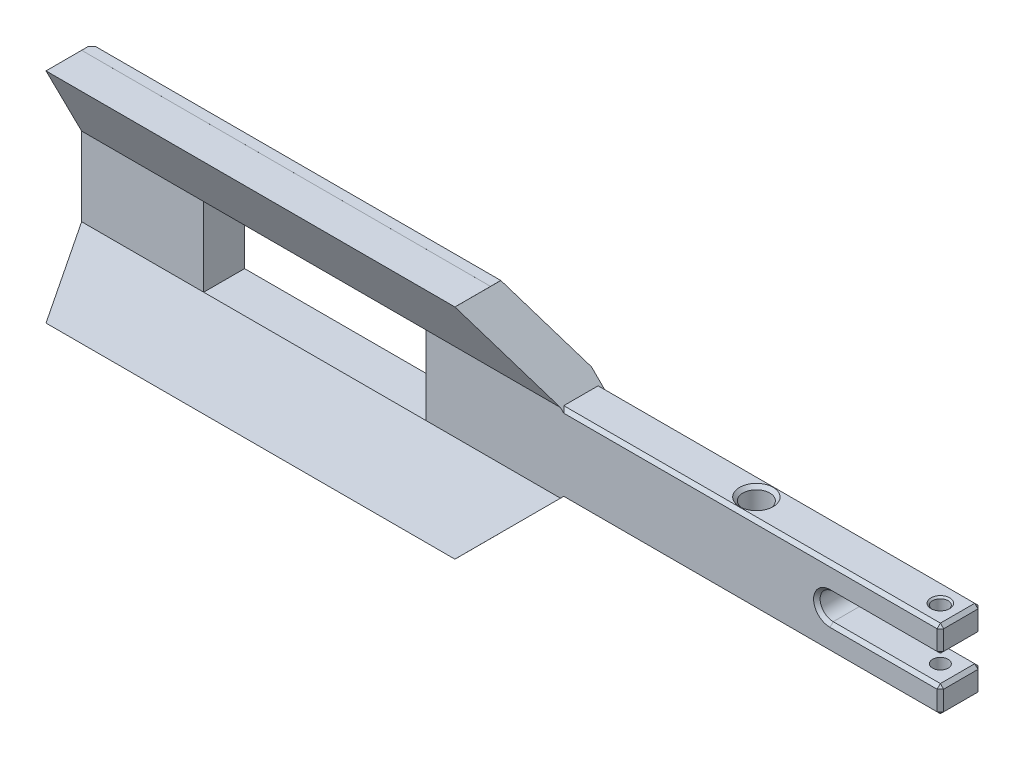
SolidWorks part; units mm, degrees
ref_plane "Front" through (0, 0, 0) normal (0, 0, 1) x (1, 0, 0)
ref_plane "Top" through (0, 0, 0) normal (0, 1, 0) x (1, 0, 0)
ref_plane "Right" through (0, 0, 0) normal (1, 0, 0) x (0, 0, -1)
sketch "Sketch1" plane through (0, 0, 0) normal (0, 0, 1) x (1, 0, 0)
  line L1 (52.5, -4.8) -> (-52.5, -4.8)
  line L2 (52.5, -4.8) -> (52.5, 4.8)
  line L3 (52.5, 4.8) -> (-52.5, 4.8)
  line L4 (-52.5, -4.8) -> (-52.5, 4.8)
  line L5 (52.5, -4.8) -> (-52.5, 4.8) construction
  line L6 (52.5, 4.8) -> (-52.5, -4.8) construction
  point P0 (0, 0)
  dimension "D1" = 9.6
  dimension "D2" = 105
extrude "Boss-Extrude1" add sketch "Sketch1" along normal blind 5
sketch "Sketch2" plane through (0, 4.8, 0) normal (0, 1, 0) x (1, 0, 0)
  line L0 (52.5, -5) -> (52.5, 0) construction
  line L2 (52.5, 0) -> (-52.5, 0) construction
  circle A0 centre (27.5, -2.5) radius 1.65
  dimension "D3" = 3.3
  dimension "D1" = 2.5
  dimension "D2" = 25
sketch "Sketch4" plane through (0, 0, 5) normal (0, 0, 1) x (1, 0, 0)
  line L0 (39, 0) -> (45, 0) construction
  line L1 (39, 1.6) -> (45, 1.6)
  line L2 (39, -1.6) -> (45, -1.6)
  arc A0 (39, 1.6) -> (39, -1.6) centre (39, 0) ccw
  arc A1 (45, -1.6) -> (45, 1.6) centre (45, 0) ccw
  point P2 (42, 0)
  dimension "D1" = 1.6
  dimension "D2" = 42
  dimension "D3" = 6
extrude "Cut-Extrude1" cut sketch "Sketch4" against normal blind 5
sketch "Sketch14" plane through (0, 0, 5) normal (0, 0, 1) x (1, 0, 0)
  line L0 (39, -1.6) -> (45, -1.6) construction
  line L1 (44.5, -1.6) -> (52.5, -1.6)
  line L2 (44.5, -1.6) -> (44.5, 1.6)
  line L3 (44.5, 1.6) -> (52.5, 1.6)
  line L4 (52.5, -1.6) -> (52.5, 1.6)
  line L5 (52.5, -4.8) -> (52.5, 4.8) construction
  line L6 (45, 1.6) -> (39, 1.6) construction
  dimension "D1" = 8
extrude "Cut-Extrude7" cut sketch "Sketch14" against normal blind 10
sketch "Sketch8" plane through (0, 0, 0) normal (0, 0, -1) x (-1, 0, 0)
  line L0 (52.5, 4.8) -> (52.5, -4.8) construction
  line L1 (52.5, 13.355) -> (2.5, 13.355)
  line L2 (52.5, 13.355) -> (52.5, -13.355)
  line L3 (52.5, -13.355) -> (2.5, -13.355)
  line L4 (2.5, 13.355) -> (2.5, -13.355)
  line L5 (2.5, 0) -> (52.5, 0) construction
  line L7 (-52.5, 0) -> (53.7381, 0) construction
  dimension "D1" = 26.71
  dimension "D3" = 50
extrude "Boss-Extrude3" add sketch "Sketch8" against normal up to surface (5 mm away) up to face at (22.675, 0, 5)
sketch "Sketch9" plane through (-52.5, 0, 0) normal (-1, 0, 0) x (0, 0, 1)
  line L0 (5, 13.355) -> (5, -13.355) construction
  line L1 (5, 13.3543) -> (9.357, 13.3543)
  line L2 (9.357, 13.3543) -> (5, 4.8)
  line L3 (5, 4.8) -> (5, 13.3543)
  line L4 (-3.9634, 0) -> (12.9509, 0) construction
  line L5 (9.357, -13.3543) -> (5, -4.8)
  line L6 (5, -13.3543) -> (9.357, -13.3543)
  line L7 (5, -4.8) -> (5, -13.3543)
  circle A0 centre (25, 0) radius 20 construction
  dimension "D1" = 40
  dimension "D2" = 9.6
  dimension "D3" = 9.6
extrude "Boss-Extrude4" add sketch "Sketch9" against normal up to surface (50 mm away) up to face at (-2.5, 9.0775, 2.5)
sketch "Sketch13" plane through (-52.5, 0, 0) normal (-1, 0, 0) x (0, 0, 1)
  line L0 (0, 6) -> (3.7462, 13.355)
  line L1 (0, 13.355) -> (0, -13.355) construction
  line L2 (5, 13.355) -> (0, 13.355) construction
  line L3 (3.7462, 13.355) -> (-2, 13.355)
  line L4 (-2, 13.355) -> (-2, -13.355)
  line L5 (-2, -13.355) -> (3.7462, -13.355)
  line L6 (5, -13.355) -> (0, -13.355) construction
  line L7 (3.7462, -13.355) -> (0, -6)
  line L8 (0, -6) -> (0, 6)
  line L10 (5, 4.8) -> (9.357, 13.3543) construction
  line L11 (9.357, -13.3543) -> (5, -4.8) construction
  dimension "D1" = 5
  dimension "D2" = 5
  dimension "D3" = 2
extrude "Cut-Extrude6" cut sketch "Sketch13" against normal through all
chamfer "Chamfer4" distance 8.55 2 edges at (-2.5, 4.8, 2.5) (-2.5, -4.8, 2.5)
sketch "Sketch10" plane through (-52.5, 0, 0) normal (-1, 0, 0) x (0, 0, 1)
  line L0 (5, 4.8) -> (5, -4.8) construction
  line L1 (5, 4.8) -> (9.357, 13.3543) construction
  line L2 (9.357, -13.3543) -> (5, -4.8) construction
  circle A0 centre (25, 0) radius 20
ref_plane "Plane1" through (-48.5, 0, 0) normal (-1, 0, 0) x (0, 0, 1)
extrude "Cut-Extrude5" cut sketch "Sketch2" against normal blind 10
chamfer "Chamfer5" distance 0.4 angle 45 20 edges at (25.85, -4.8, 2.5) (25.85, 4.8, 2.5) (52.5, 4.8, 2.5) (29.275, 4.8, 5) (52.5, -3.2, 5) (52.5, 3.2, 5) (29.275, -4.8, 5) (52.5, -4.8, 2.5) (29.275, 4.8, 0) (29.275, -4.8, 0) (52.5, 3.2, 0) (52.5, -3.2, 0) (45.75, -1.6, 0) (37.4, 0, 0) (45.75, 1.6, 0) (45.75, 1.6, 5) (37.4, 0, 5) (45.75, -1.6, 5) (52.5, 1.6, 2.5) (52.5, -1.6, 2.5)
chamfer "Chamfer6" distance 0.4 angle 45 3 edges at (-52.5, 9.6775, 1.8731) (-52.5, -9.6775, 1.8731) (-52.5, 0, 0)
sketch "Sketch15" plane through (0, -4.8, 0) normal (0, -1, 0) x (1, 0, 0)
  line L0 (52.5, 4.6) -> (52.5, 0.4) construction
  line L1 (52.1, 0) -> (6.45, 0) construction
  circle A0 centre (50, 2.5) radius 0.95
  dimension "D1" = 1.9
  dimension "D2" = 2.5
  dimension "D3" = 2.5
extrude "Cut-Extrude8" cut sketch "Sketch15" against normal blind 10
chamfer "Chamfer11" distance 0.2 angle 45 2 edges at (50.95, 4.8, 2.5) (50.95, -4.8, 2.5)
sketch "Sketch16" plane through (0, 0, 5) normal (0, 0, 1) x (1, 0, 0)
  line L1 (-10.4, 4.8) -> (-37.5733, 4.8)
  line L3 (-37.5733, -4.8) -> (-10.4, -4.8)
  line L7 (6.05, 4.8) -> (-52.5, 4.8) construction
  line L8 (6.05, -4.8) -> (-52.5, -4.8) construction
  line L11 (-37.5733, 4.8) -> (-37.5733, -4.8)
  line L12 (-10.4, 4.8) -> (-10.4, -4.8)
extrude "Cut-Extrude9" cut sketch "Sketch16" against normal blind 10
sketch "Sketch17" plane through (0, 0, 0) normal (0, 0, 1) x (1, 0, 0)
  line L13 (29.15, -4.4) -> (29.15, 4.4) construction
  circle A0 centre (-2.5, -0.2) radius 2.55
  dimension "D1" = 31.65
extrude "Boss-Extrude5" add sketch "Sketch17" against normal blind 4
fillet "Fillet2" radius 0.25 1 edges at (0.05, -0.2, -4)
